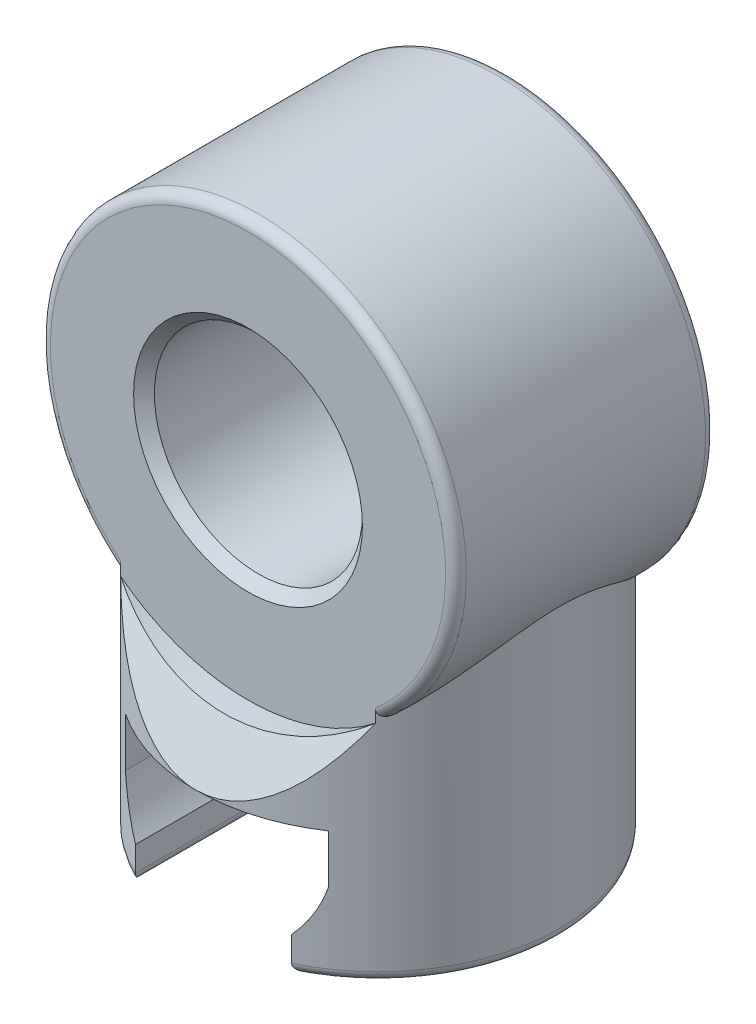
SolidWorks part; units mm, degrees
ref_plane "前视基准面" through (0, 0, 0) normal (0, 0, 1) x (1, 0, 0)
ref_plane "上视基准面" through (0, 0, 0) normal (0, 1, 0) x (1, 0, 0)
ref_plane "右视基准面" through (0, 0, 0) normal (1, 0, 0) x (0, 0, -1)
sketch "草图1" plane through (0, 0, 0) normal (0, 0, 1) x (1, 0, 0)
  circle A0 centre (0, 0) radius 2
  circle A1 centre (0, 0) radius 4
  dimension "D1" = 4
  dimension "D2" = 8
extrude "凸台-拉伸1" add sketch "草图1" along normal blind 2.5 and the other way blind 2.5
ref_plane "基准面1" through (0, -7.5, 0) normal (0, 1, 0) x (1, 0, 0)
sketch "草图2" plane through (0, -7.5, 0) normal (0, 1, 0) x (1, 0, 0)
  circle A1 centre (0, 0) radius 3.5
extrude "凸台-拉伸2" add sketch "草图2" along normal up to surface (3.5 mm away) up to face at (4, 0, -2.5)
sketch "草图3" plane through (0, 0, 0) normal (0, 0, 1) x (1, 0, 0)
  line L0 (0, -7.5) -> (0, -5.5) construction
  line L1 (-3.5, -7.5) -> (3.5, -7.5) construction
  line L2 (0, -5.5) -> (0, -5) construction
  line L3 (-1.5, -7.5) -> (1.5, -7.5)
  line L4 (1.5, -7.5) -> (1.5, -6.8229)
  line L5 (-1.95, -5) -> (1.95, -5)
  line L6 (1.95, -5) -> (1.95, -5.9444)
  line L7 (-1.95, -5) -> (-1.95, -5.9444)
  line L8 (-1.5, -7.5) -> (-1.5, -6.8229)
  arc A0 (1.5, -6.8229) -> (1.95, -5.9444) centre (0, -5.5) ccw
  arc A1 (-1.5, -6.8229) -> (-1.95, -5.9444) centre (0, -5.5) cw
  dimension "D5" = 2
  dimension "D1" = 2
  dimension "D2" = 0.5
  dimension "D3" = 1.5
  dimension "D4" = 1.95
extrude "切除-拉伸1" cut sketch "草图3" along normal up to next
sketch "草图4" plane through (0, 0, 0) normal (1, 0, 0) x (0, 0, -1)
  line L0 (-3.5, -5) -> (-2.5, -3.1623)
  line L1 (-2.5, -3.1623) -> (-3.5, -3.1623)
  line L2 (-3.5, -5) -> (-3.5, -3.1623)
extrude "切除-拉伸2" cut sketch "草图4" against normal up to next and the other way up to next
mirror "镜向1" about plane through (0, 0, 0) normal (0, 0, 1) of "切除-拉伸2"
sketch "草图6" plane through (0, 0, 0) normal (0, 0, 1) x (1, 0, 0)
  line L0 (0, -5) -> (0, -7.5)
  line L6 (-1.95, -5) -> (-1.95, -5.9444)
  line L7 (-1.5, -6.8229) -> (-1.5, -7.5)
  line L8 (-1.5, -7.5) -> (1.5, -7.5)
  line L9 (1.5, -7.5) -> (1.5, -6.8229)
  line L10 (1.95, -5.9444) -> (1.95, -5)
  line L11 (1.95, -5) -> (-1.95, -5)
  line L12 (-1.95, -5) -> (-1.95, -5.9444)
  line L13 (-1.5, -6.8229) -> (-1.5, -7.5)
  line L14 (-1.5, -7.5) -> (0, -7.5)
  line L17 (0, -5) -> (-1.95, -5)
  arc A2 (-1.95, -5.9444) -> (-1.5, -6.8229) centre (0, -5.5) ccw
  arc A3 (1.5, -6.8229) -> (1.95, -5.9444) centre (0, -5.5) ccw
  arc A4 (-1.95, -5.9444) -> (-1.5, -6.8229) centre (0, -5.5) ccw
  dimension "D1" = 0
revolve "切除-旋转2" cut sketch "草图6" angle 360 about L0
chamfer "倒角1" distance 0.2 angle 45 2 edges at (2, 0, -2.5) (2, 0, 2.5)
fillet "圆角1" radius 0.2 2 edges at (0, 4, -2.5) (0, 4, 2.5)
fillet "圆角2" radius 0.2 4 edges at (0, -7.5, -3.5) (-1.5, -7.5, 1.5811) (0, -7.5, -1.5) (1.5, -7.5, 1.5811)
